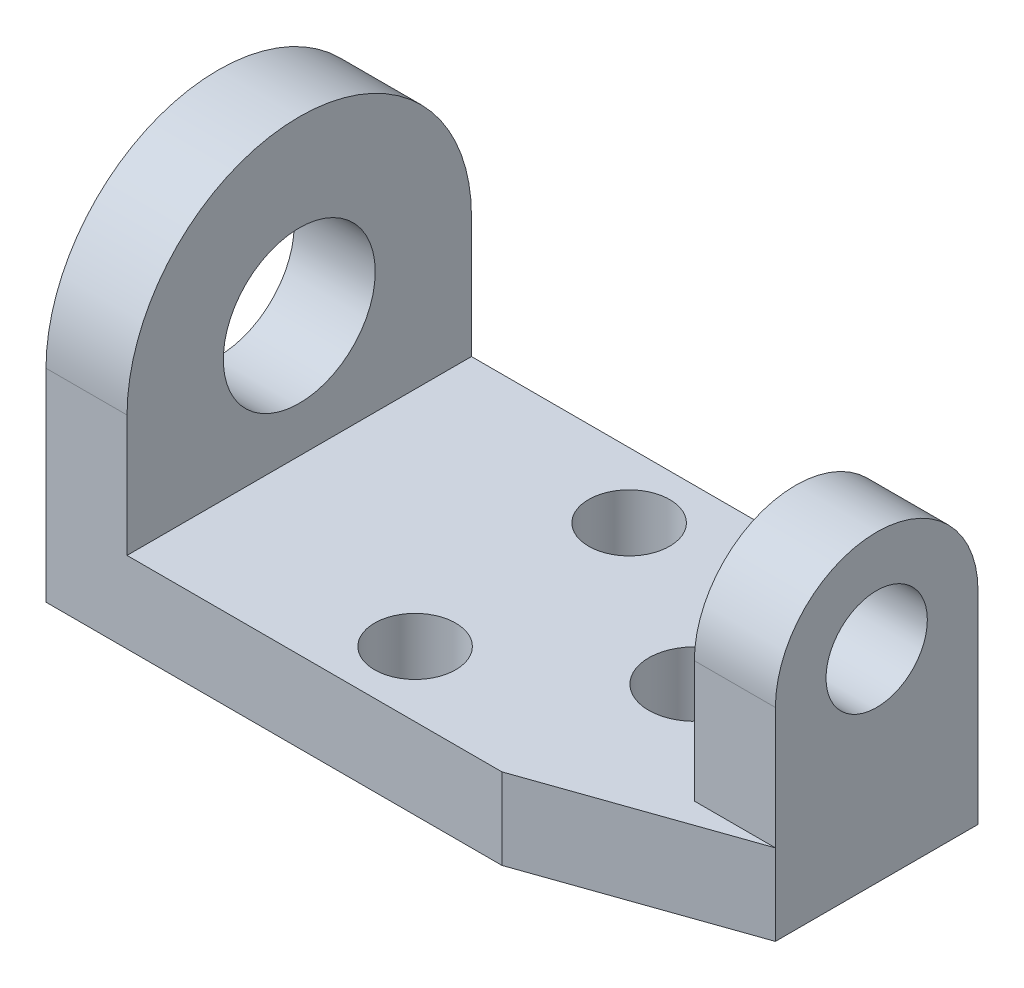
SolidWorks part; units mm, degrees
ref_plane "Front Plane" through (0, 0, 0) normal (0, 0, 1) x (1, 0, 0)
ref_plane "Top Plane" through (0, 0, 0) normal (0, 1, 0) x (1, 0, 0)
ref_plane "Right Plane" through (0, 0, 0) normal (1, 0, 0) x (0, 0, -1)
sketch "Sketch1" plane through (0, 0, 0) normal (0, 1, 0) x (1, 0, 0)
  line L4 (0, -17) -> (0, 17)
  line L5 (0, 17) -> (45, 17)
  line L6 (45, 17) -> (65, 10)
  line L10 (65, 10) -> (65, -10)
  line L11 (0, 0) -> (65, 0) construction
  line L12 (45, -17) -> (65, -10)
  line L13 (0, -17) -> (45, -17)
  line L14 (30, 10.563) -> (30, -10.563) construction
  line L15 (0, 17) -> (8, 17)
  line L16 (0, 17) -> (0, -17)
  line L17 (0, -17) -> (8, -17)
  line L18 (8, 17) -> (8, -17)
  line L20 (65, 10) -> (57, 10)
  line L21 (65, 10) -> (65, -10)
  line L22 (65, -10) -> (57, -10)
  line L23 (57, 10) -> (57, -10)
  circle A0 centre (47, 0) radius 4.5
  circle A1 centre (30, 10.563) radius 4
  circle A2 centre (30, -10.563) radius 4
  dimension "D7" = 8
  dimension "D9" = 9
  dimension "D1" = 65
  dimension "D2" = 45
  dimension "D3" = 10
  dimension "D4" = 34
  dimension "D5" = 8
  dimension "D6" = 22
  dimension "D8" = 17
  dimension "D10" = 8
extrude "Boss-Extrude1" add sketch "Sketch1" along normal blind 8 contours L23 L20 L6 L5 L18 L13 L12 L22 A0 A1 A2 | L18 L5 L4 L13 | L20 L23 L22 L10 region at (4, 0, 0) region at (31.7565, 0, 0) region at (61, 0, 0)
extrude "Boss-Extrude2" add sketch "Sketch1<4>" along normal blind 37 contours L18 L5 L4 L13 region at (4, 0, 0)
sketch "Sketch1<4>" plane through (0, 0, 0) normal (0, 1, 0) x (1, 0, 0) same geometry as "Sketch1"
extrude "Boss-Extrude3" add sketch "Sketch1<5>" along normal blind 30 contours L20 L23 L22 L10 region at (61, 0, 0)
sketch "Sketch1<5>" plane through (0, 0, 0) normal (0, 1, 0) x (1, 0, 0) same geometry as "Sketch1"
sketch "Sketch4" plane through (65, 0, 0) normal (1, 0, 0) x (0, 0, -1)
  line L0 (0, 0) -> (0, 20) construction
  circle A0 centre (0, 20) radius 10
  circle A1 centre (0, 20) radius 5
  line M3 (10, 8) -> (10, 30)
  line M4 (10, 30) -> (-10, 30)
  line M5 (-10, 30) -> (-10, 8)
  dimension "D2" = 10
  dimension "D1" = 20
extrude "Cut-Extrude1" cut sketch "Sketch4" against normal up to surface (8 mm away) contours A0 M4 M5 | A0 M3 M4 | A1 region at (65, 27.7663, -7.7663) region at (65, 27.7663, 7.7663) region at (65, 20, 0) up to face at (57, 19, 0)
sketch "Sketch5" plane through (8, 0, 0) normal (1, 0, 0) x (0, 0, -1)
  circle A0 centre (0, 20) radius 17
  circle A1 centre (0, 20) radius 7.5
  line M1 (-17, 37) -> (-17, 8)
  line M3 (17, 8) -> (17, 37)
  line M4 (17, 37) -> (-17, 37)
  dimension "D1" = 15
extrude "Cut-Extrude2" cut sketch "Sketch5" against normal through all contours A0 M4 M1 | A0 M3 M4 | A1 region at (8, 33.2027, -13.2027) region at (8, 33.2027, 13.2027) region at (8, 20, 0)
